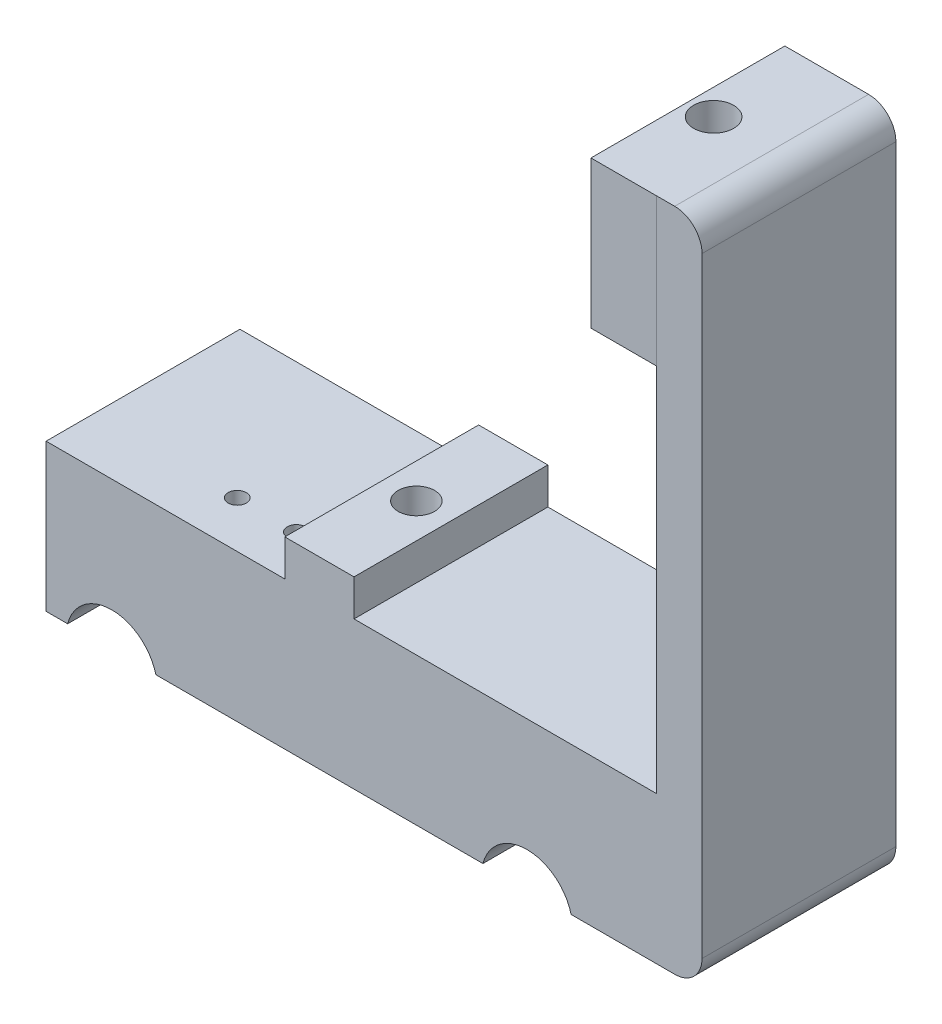
SolidWorks part; units mm, degrees
ref_plane "Front Plane" through (0, 0, 0) normal (0, 0, 1) x (1, 0, 0)
ref_plane "Top Plane" through (0, 0, 0) normal (0, 1, 0) x (1, 0, 0)
ref_plane "Right Plane" through (0, 0, 0) normal (1, 0, 0) x (0, 0, -1)
sketch "Sketch2" plane through (0, 0, 0) normal (0, 0, 1) x (1, 0, 0)
  line L0 (10.1, 0) -> (-10.1, 0)
  line L1 (-10.1, 0) -> (-10.1, 1.7099)
  line L2 (-10.1, 1.7099) -> (-6.2548, 7)
  line L3 (-6.2548, 7) -> (6.2548, 7)
  line L4 (0, 7) -> (0, 0)
  line L5 (0, 0) -> (0, 9.2516) construction
  line L6 (10.1, 1.7099) -> (6.2548, 7)
  line L7 (10.1, 0) -> (10.1, 1.7099)
  dimension "D1" = 20.2
  dimension "D2" = 7
extrude "Boss-Extrude1" add sketch "Sketch2" along normal blind 10.8 contours L4 L3 L2 L1 L0 | L0 L7 L6 L3 L4 region at (4.4168, 3.2082, 0) region at (-4.4168, 3.2082, 0)
sketch "Sketch4" plane through (0, 0, 0) normal (0, 0, 1) x (1, 0, 0)
  line L0 (-3.8, 0) -> (-3.8, -4.8)
  line L1 (10.1, 0) -> (-10.1, 0) construction
  line L2 (-3.8, -4.8) -> (-30, -4.8)
  line L3 (-30, -4.8) -> (-30, -29.8)
  line L4 (-30, -29.8) -> (30, -29.8)
  line L5 (0, 0) -> (0, -29.8) construction
  line L6 (0, -29.8) -> (0, 0)
  line L7 (3.8, 0) -> (-3.8, 0)
  line L8 (0, 0) -> (0, -30.5381) construction
  line L9 (30, -4.8) -> (30, -29.8)
  line L10 (3.8, -4.8) -> (30, -4.8)
  line L11 (3.8, 0) -> (3.8, -4.8)
  line L13 (-30, -20.98) -> (30, -20.98)
  line L14 (-30, -20.98) -> (-30, -23.48)
  line L15 (-30, -23.48) -> (30, -23.48)
  line L16 (30, -20.98) -> (30, -23.48)
  dimension "D1" = 4.8
  dimension "D2" = 3.8
  dimension "D3" = 25
  dimension "D4" = 60
  dimension "D6" = 8.82
extrude "Boss-Extrude2" add sketch "Sketch4" along normal mid plane 21.28 contours L6 L7 L0 L2 L3 L4 | L11 L7 L6 L4 L9 L10 region at (-14.5256, -12.5101, 0) region at (14.5256, -12.5101, 0)
sketch "Sketch5" plane through (0, 0, 0) normal (0, 0, 1) x (1, 0, 0)
  line L0 (-29.791, -22.2274) -> (26.9734, -22.2274) construction
  line L3 (0, -20.98) -> (0, 7) construction
  line L5 (-6.2548, 7) -> (6.2548, 7) construction
  line L20 (-30, -20.98) -> (30, -20.98) construction
  circle A0 centre (-22.791, -22.2274) radius 5
  circle A1 centre (22.791, -22.2274) radius 5
  dimension "D1" = 7
extrude "Cut-Extrude1" cut sketch "Sketch5" along normal through all both and the other way through all
fillet "Fillet1" radius 1 6 edges at (-10.1, 0, 5.4) (-10.1, 1.7099, 5.4) (-6.2548, 7, 5.4) (6.2548, 7, 5.4) (10.1, 0, 5.4) (10.1, 1.7099, 5.4)
sketch "Sketch6" plane through (30, 0, 0) normal (1, 0, 0) x (0, 0, -1)
  line L0 (-10.64, -20.98) -> (10.64, -20.98) construction
  line L1 (-10.64, -4.8) -> (10.64, -4.8)
  line L2 (-10.64, -4.8) -> (-10.64, -20.98)
  line L3 (-10.64, -20.98) -> (10.64, -20.98)
  line L4 (10.64, -4.8) -> (10.64, -20.98)
extrude "Boss-Extrude3" add sketch "Sketch6" along normal blind 12
sketch "Sketch7" plane through (0, -4.8, 0) normal (0, 1, 0) x (1, 0, 0)
  line L0 (3.8, -10.64) -> (42, -10.64) construction
  line L1 (42, 10.6413) -> (37, 10.6413)
  line L2 (42, 10.6413) -> (42, -10.64)
  line L3 (42, -10.64) -> (37, -10.64)
  line L4 (37, 10.6413) -> (37, -10.64)
  dimension "D1" = 5
extrude "Boss-Extrude4" add sketch "Sketch7" along normal blind 56.83
sketch "Sketch8" plane through (37, 0, 0) normal (-1, 0, 0) x (0, 0, 1)
  line L0 (-10.6413, 52.03) -> (-10.6413, -4.8) construction
  line L1 (10.643, 52.03) -> (-10.6413, 52.03)
  line L2 (10.643, 52.03) -> (10.643, 35.85)
  line L3 (10.643, 35.85) -> (-10.6413, 35.85)
  line L4 (-10.6413, 52.03) -> (-10.6413, 35.85)
  dimension "D1" = 16.18
extrude "Boss-Extrude5" add sketch "Sketch8" along normal blind 7.19
fillet "Fillet3" radius 3 2 edges at (42, 52.03, -0.0007) (42, -20.98, 0)
sketch "Sketch9" plane through (0, -20.98, 0) normal (0, -1, 0) x (1, 0, 0)
  line L0 (27.6329, 0) -> (27.6329, 10.8) construction
  line L2 (27.6329, 10.64) -> (39, 10.64) construction
  circle A0 centre (32.6329, 0) radius 2.2
  dimension "D1" = 5
  dimension "D2" = 10.64
extrude "Cut-Extrude2" cut sketch "Sketch9" against normal through all
sketch "Sketch10" plane through (0, -20.98, 0) normal (0, -1, 0) x (1, 0, 0)
  line L2 (-17.9491, 0) -> (-17.9491, 10.8) construction
  line L3 (-17.9491, 10.64) -> (17.9491, 10.64) construction
  circle A0 centre (0.0009, 0) radius 2
  dimension "D1" = 10.64
  dimension "D2" = 17.95
extrude "Cut-Extrude3" cut sketch "Sketch10" against normal through all
sketch "Sketch11" plane through (0, 0, 10.8) normal (0, 0, 1) x (1, 0, 0)
  line L0 (9.1, 0) -> (-9.1, 0) construction
  line L1 (-12.6098, 8.9215) -> (12.3675, 8.9215)
  line L2 (-12.6098, 8.9215) -> (-12.6098, -0.8)
  line L3 (-12.6098, -0.8) -> (12.3675, -0.8)
  line L4 (12.3675, 8.9215) -> (12.3675, -0.8)
  dimension "D1" = 0.8
extrude "Cut-Extrude4" cut sketch "Sketch11" against normal through all
sketch "Sketch12" plane through (0, -20.98, 0) normal (0, -1, 0) x (1, 0, 0)
  arc A0 (-8.6262, 5.538) -> (-6.6262, 5.538) centre (-7.6262, 5.538) ccw construction
  arc A1 (-6.6262, 5.538) -> (-8.6262, 5.538) centre (-7.6262, 5.538) ccw construction
  arc A2 (-15.1262, 5.538) -> (-13.1262, 5.538) centre (-14.1262, 5.538) ccw construction
  arc A3 (-13.1262, 5.538) -> (-15.1262, 5.538) centre (-14.1262, 5.538) ccw construction
  arc A4 (-8.6262, 5.538) -> (-6.6262, 5.538) centre (-7.6262, 5.538) ccw
  arc A5 (-6.6262, 5.538) -> (-8.6262, 5.538) centre (-7.6262, 5.538) ccw
  arc A6 (-15.1262, 5.538) -> (-13.1262, 5.538) centre (-14.1262, 5.538) ccw
  arc A7 (-13.1262, 5.538) -> (-15.1262, 5.538) centre (-14.1262, 5.538) ccw
extrude "Cut-Extrude5" cut sketch "Sketch12" against normal up to next
